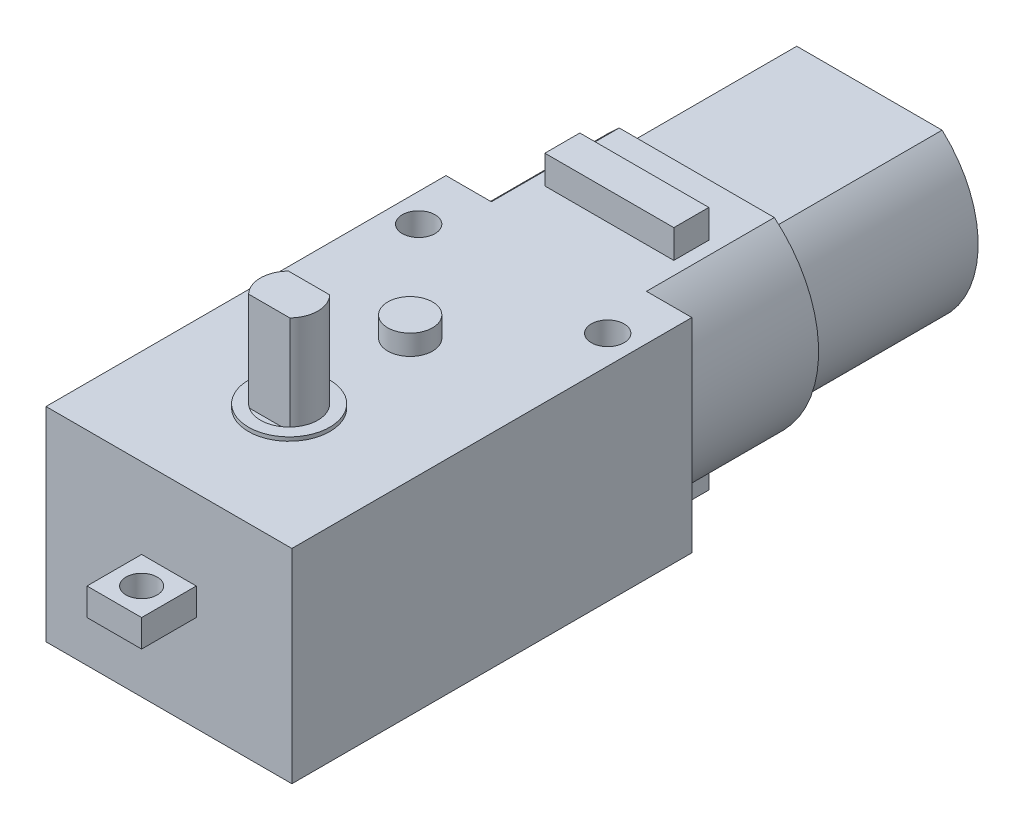
SolidWorks part; units mm, degrees
note: The reader was unsure of these and kept them because the rebuilt part matched: shared geometry of "Sketch1<3>", "Sketch1<4>", "Sketch1<5>", "Sketch1<6>", "Sketch1<7>".
ref_plane "Front Plane" through (0, 0, 0) normal (0, 0, 1) x (1, 0, 0)
ref_plane "Top Plane" through (0, 0, 0) normal (0, 1, 0) x (1, 0, 0)
ref_plane "Right Plane" through (0, 0, 0) normal (1, 0, 0) x (0, 0, -1)
sketch "Sketch1" plane through (0, 0, 0) normal (0, 1, 0) x (1, 0, 0)
  line L0 (0, -3.725) -> (0, 13.125) construction
  line L1 (-11.25, -11) -> (11.25, -11)
  line L2 (-11.25, -11) -> (-11.25, 25.6)
  line L3 (-11.25, 25.6) -> (11.25, 25.6)
  line L4 (11.25, -11) -> (11.25, 25.6)
  line L5 (-11.25, -11) -> (11.25, 25.6) construction
  line L6 (-11.25, 25.6) -> (11.25, -11) construction
  line L8 (-11.15, 37.3) -> (11.15, 37.3)
  line L9 (-11.15, 37.3) -> (-11.15, 25.6)
  line L10 (-11.15, 25.6) -> (11.15, 25.6)
  line L11 (11.15, 37.3) -> (11.15, 25.6)
  line L12 (-11.15, 37.3) -> (11.15, 25.6) construction
  line L13 (-11.15, 25.6) -> (11.15, 37.3) construction
  line L14 (-9.7, 53.3) -> (9.7, 53.3)
  line L15 (-9.7, 53.3) -> (-9.7, 37.3)
  line L16 (-9.7, 37.3) -> (9.7, 37.3)
  line L17 (9.7, 53.3) -> (9.7, 37.3)
  line L18 (-9.7, 53.3) -> (9.7, 37.3) construction
  line L19 (-9.7, 37.3) -> (9.7, 53.3) construction
  line L20 (-5.9, 32.5) -> (5.9, 32.5)
  line L21 (-5.9, 32.5) -> (-5.9, 29.3)
  line L22 (-5.9, 29.3) -> (5.9, 29.3)
  line L23 (5.9, 32.5) -> (5.9, 29.3)
  line L24 (-5.9, 32.5) -> (5.9, 29.3) construction
  line L25 (-5.9, 29.3) -> (5.9, 32.5) construction
  line L26 (-1.8868, -1.825) -> (1.8868, -1.825)
  line L28 (-1.8868, 1.825) -> (1.8868, 1.825)
  line L30 (-1.8868, -1.825) -> (1.8868, 1.825) construction
  line L31 (-1.8868, 1.825) -> (1.8868, -1.825) construction
  circle A0 centre (0, 0) radius 3.725
  circle A1 centre (0, 11.075) radius 2.05
  circle A2 centre (0, 0) radius 2.625
  point P0 (0, 7.3)
  point P12 (0, 31.45)
  point P17 (0, 45.3)
  point P22 (0, 30.9)
  point P32 (0, 0)
  point P33 (0, 0)
  dimension "D3" = 11
  dimension "D4" = 7.45
  dimension "D5" = 16.85
  dimension "D6" = 4.1
  dimension "D14" = 5.25
  dimension "D1" = 36.6
  dimension "D2" = 22.5
  dimension "D7" = 22.3
  dimension "D8" = 19.4
  dimension "D9" = 11.7
  dimension "D10" = 16
  dimension "D11" = 40.3
  dimension "D12" = 3.2
  dimension "D13" = 11.8
  dimension "D15" = 3.65
extrude "Boss-Extrude1" add sketch "Sketch1" against normal blind 18.65 contours L4 L3 L2 L1
extrude "Boss-Extrude2" add sketch "Sketch1<3>" against normal blind 17.2 contours L8 L11 L10 L9
sketch "Sketch1<3>" plane through (0, 0, 0) normal (0, 1, 0) x (1, 0, 0) same geometry as "Sketch1"
extrude "Boss-Extrude3" add sketch "Sketch1<4>" along normal blind 2.6 contours L23 L20 L21 L22
sketch "Sketch1<4>" plane through (0, 0, 0) normal (0, 1, 0) x (1, 0, 0) same geometry as "Sketch1"
sketch "Sketch3" plane through (0, 0, -25.6) normal (0, 0, -1) x (-1, 0, 0)
  line L0 (11.15, -8.6) -> (-11.15, -8.6) construction
  line L1 (11.15, -17.2) -> (11.15, 0) construction
  line L2 (-11.15, -17.2) -> (-11.15, 0) construction
  line L3 (11.15, -17.2) -> (-11.15, -17.2) construction
  line L4 (11.15, 0) -> (-11.15, 0) construction
  line L5 (7.0967, -17.2) -> (-11.15, -17.2)
  line L6 (11.15, 0) -> (-11.15, 0)
  arc A0 (-7.0967, 0) -> (-7.0967, -17.2) centre (0, -8.6) ccw
  arc A1 (7.0967, -17.2) -> (7.0967, 0) centre (0, -8.6) ccw
extrude "Cut-Extrude1" cut sketch "Sketch3" along normal up to next
sketch "Sketch4" plane through (0, 0, -37.3) normal (0, 0, -1) x (-1, 0, 0)
  line L42 (6.6515, -1.2) -> (-6.6515, -1.2)
  line L43 (-6.6515, -16) -> (6.6515, -16)
  line L44 (6.6515, -1.2) -> (-6.6515, -1.2)
  line L45 (-6.6515, -16) -> (6.6515, -16)
  arc A37 (6.6515, -16) -> (6.6515, -1.2) centre (0, -8.6) ccw
  arc A38 (-6.6515, -1.2) -> (-6.6515, -16) centre (0, -8.6) ccw
  arc A39 (6.6515, -16) -> (6.6515, -1.2) centre (0, -8.6) ccw
  arc A40 (-6.6515, -1.2) -> (-6.6515, -16) centre (0, -8.6) ccw
  dimension "D1" = 1.2
extrude "Boss-Extrude4" add sketch "Sketch4" along normal blind 15.8
sketch "Sketch5" plane through (0, 0, -53.1) normal (0, 0, -1) x (-1, 0, 0)
  line L0 (9.95, -8.6) -> (-9.95, -8.6) construction
  arc A0 (6.6515, -16) -> (6.6515, -1.2) centre (0, -8.6) ccw construction
  arc A1 (-6.6515, -1.2) -> (-6.6515, -16) centre (0, -8.6) ccw construction
  circle A2 centre (0, -8.6) radius 1
  point P10 (0, 0)
  point P11 (0, 0)
  dimension "D1" = 2
extrude "Boss-Extrude5" add sketch "Sketch5" along normal blind 1.25
ref_plane "Plane1" through (0, -8.6, 0) normal (0, 1, 0) x (1, 0, 0)
mirror "Mirror1" about plane through (0, -8.6, 0) normal (0, 1, 0) of "Boss-Extrude3"
sketch "Sketch6" plane through (0, 0, 11) normal (0, 0, 1) x (1, 0, 0)
  line L1 (-2.5, -7.35) -> (2.5, -7.35)
  line L2 (-2.5, -7.35) -> (-2.5, -9.85)
  line L3 (-2.5, -9.85) -> (2.5, -9.85)
  line L4 (2.5, -7.35) -> (2.5, -9.85)
  line L5 (-2.5, -7.35) -> (2.5, -9.85) construction
  line L6 (-2.5, -9.85) -> (2.5, -7.35) construction
  point P0 (0, -8.6)
  point P5 (0, 0)
  point P7 (0, 0)
  dimension "D1" = 5
  dimension "D2" = 2.5
extrude "Boss-Extrude6" add sketch "Sketch6" along normal blind 5
sketch "Sketch7" plane through (0, -7.35, 0) normal (0, 1, 0) x (1, 0, 0)
  line L0 (-2.5, -16) -> (-2.5, -11) construction
  line L1 (2.5, -16) -> (-2.5, -16) construction
  circle A0 centre (0, -13.5) radius 1.425
  point P4 (-2.5, -13.5)
  point P7 (0, -16)
  dimension "D1" = 2.85
extrude "Cut-Extrude2" cut sketch "Sketch7" against normal up to next
extrude "Boss-Extrude7" add sketch "Sketch1<5>" along normal blind 0.35 contours A0 A2
sketch "Sketch1<5>" plane through (0, 0, 0) normal (0, 1, 0) x (1, 0, 0) same geometry as "Sketch1"
extrude "Boss-Extrude8" add sketch "Sketch1<6>" along normal blind 1.85 contours A1
sketch "Sketch1<6>" plane through (0, 0, 0) normal (0, 1, 0) x (1, 0, 0) same geometry as "Sketch1"
extrude "Boss-Extrude9" add sketch "Sketch1<7>" along normal blind 9 contours L26 A2 L28
sketch "Sketch1<7>" plane through (0, 0, 0) normal (0, 1, 0) x (1, 0, 0) same geometry as "Sketch1"
sketch "Sketch8" plane through (0, -18.65, 0) normal (0, -1, 0) x (1, 0, 0)
  line L0 (10.15, -20.5) -> (11.25, -20.5) construction
  line L1 (11.25, 11) -> (11.25, -25.6) construction
  line L2 (-10.15, -20.5) -> (-11.25, -20.5) construction
  line L3 (-11.25, 11) -> (-11.25, -25.6) construction
  line L4 (-8.65, -22) -> (-8.65, -25.6) construction
  line L5 (-11.25, -25.6) -> (11.25, -25.6) construction
  line L6 (8.65, -22) -> (8.65, -25.6) construction
  line L7 (7.0967, -25.6) -> (11.15, -25.6) construction
  circle A0 centre (8.65, -20.5) radius 1.5
  circle A1 centre (-8.65, -20.5) radius 1.5
  dimension "D2" = 3
  dimension "D1" = 1.1
  dimension "D3" = 3.6
extrude "Cut-Extrude3" cut sketch "Sketch8" against normal up to next
